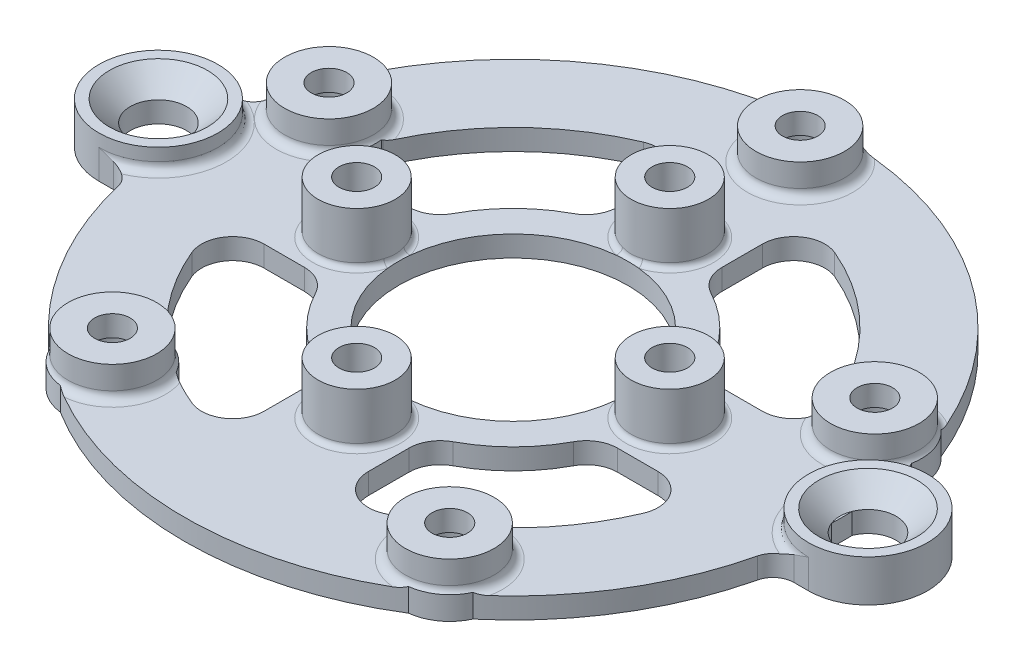
SolidWorks part; units mm, degrees
material "ABS"
ref_plane "Plan de face" through (0, 0, 0) normal (0, 0, 1) x (1, 0, 0)
ref_plane "Plan de dessus" through (0, 0, 0) normal (0, 1, 0) x (1, 0, 0)
ref_plane "Plan de droite" through (0, 0, 0) normal (1, 0, 0) x (0, 0, -1)
sketch "Esquisse1" plane through (0, 0, 0) normal (0, 1, 0) x (1, 0, 0)
  circle A0 centre (0, 0) radius 15 construction
  circle A1 centre (0, 15) radius 1.7
  circle A2 centre (0, 0) radius 31.5
  circle A3 centre (15, 0) radius 1.7
  circle A4 centre (0, -15) radius 1.7
  circle A5 centre (-15, 0) radius 1.7
  circle A6 centre (0, 0) radius 11
  point P15 (0, 0)
  dimension "D1" = 3.4
  dimension "D2" = 30
  dimension "D4" = 22
  dimension "D5" = 63
  dimension "D3" = 4
extrude "Boss.-Extru.1" add sketch "Esquisse1" along normal blind 2
sketch "Esquisse2" plane through (0, 2, 0) normal (0, 1, 0) x (1, 0, 0)
  circle A0 centre (0, -15) radius 1.7 construction
  circle A1 centre (15, 0) radius 1.7 construction
  circle A2 centre (0, 15) radius 1.7 construction
  circle A3 centre (-15, 0) radius 1.7 construction
  circle A4 centre (0, -15) radius 1.7
  circle A5 centre (15, 0) radius 1.7
  circle A6 centre (0, 15) radius 1.7
  circle A7 centre (-15, 0) radius 1.7
  circle A8 centre (0, -15) radius 3.7
  circle A9 centre (15, 0) radius 3.7
  circle A10 centre (0, 15) radius 3.7
  circle A11 centre (-15, 0) radius 3.7
  dimension "D1" = 2
extrude "Boss.-Extru.2" add sketch "Esquisse2" along normal blind 5
sketch "Esquisse3" plane through (0, 0, 0) normal (0, -1, 0) x (1, 0, 0)
  circle A0 centre (15, 0) radius 3
  circle A1 centre (0, -15) radius 3
  circle A2 centre (-15, 0) radius 3
  circle A3 centre (0, 15) radius 3
  point P12 (0, 0)
  dimension "D1" = 6
  dimension "D2" = 4
extrude "Enlèv. mat.-Extru.1" cut sketch "Esquisse3" against normal blind 3
fillet "Congé1" radius 0.5 4 edges at (-15, 2, 3.7) (0, 2, -11.3) (15, 2, 3.7) (0, 2, 18.7)
sketch "Esquisse4" plane through (0, 2, 0) normal (0, 1, 0) x (1, 0, 0)
  line L0 (0, 0) -> (0, -38.4665) construction
  line L1 (34, 0) -> (26, 0) construction
  line L2 (34, -5.7) -> (26, -5.7)
  line L3 (34, 5.7) -> (26, 5.7)
  line L4 (-34, 0) -> (-26, 0) construction
  line L5 (-34, -5.7) -> (-26, -5.7)
  line L6 (-34, 5.7) -> (-26, 5.7)
  circle A0 centre (34, 0) radius 2.7
  arc A2 (34, -5.7) -> (34, 5.7) centre (34, 0) ccw
  arc A3 (26, 5.7) -> (26, -5.7) centre (26, 0) ccw
  arc A4 (-34, -5.7) -> (-34, 5.7) centre (-34, 0) cw
  arc A5 (-26, 5.7) -> (-26, -5.7) centre (-26, 0) cw
  circle A6 centre (-34, 0) radius 2.7
  point P7 (30, 0)
  point P15 (-30, 0)
  dimension "D1" = 5.4
  dimension "D3" = 3
  dimension "D2" = 68
  dimension "D4" = 8
extrude "Boss.-Extru.3" add sketch "Esquisse4" against normal blind 2
sketch "Esquisse5" plane through (0, 2, 0) normal (0, 1, 0) x (1, 0, 0)
  circle A0 centre (-34, 0) radius 2.7 construction
  circle A1 centre (34, 0) radius 2.7 construction
  circle A2 centre (-34, 0) radius 2.7
  circle A3 centre (34, 0) radius 2.7
  circle A4 centre (-34, 0) radius 5.7
  circle A5 centre (34, 0) radius 5.7
  dimension "D1" = 3
extrude "Boss.-Extru.4" add sketch "Esquisse5" along normal blind 2
chamfer "Chanfrein1" distance 2 angle 45 2 edges at (-34, 4, 2.7) (34, 4, 2.7)
sketch "Esquisse6" plane through (0, 2, 0) normal (0, 1, 0) x (1, 0, 0)
  circle A0 centre (0, 0) radius 27.5 construction
  circle A1 centre (0, 27.5) radius 1.7
  circle A2 centre (0, 27.5) radius 2.5 construction
  circle A3 centre (0, 0) radius 25 construction
  circle A4 centre (26.1541, 8.498) radius 1.7
  circle A5 centre (26.1541, 8.498) radius 2.5 construction
  circle A6 centre (16.1641, -22.248) radius 1.7
  circle A7 centre (16.1641, -22.248) radius 2.5 construction
  circle A8 centre (-16.1641, -22.248) radius 1.7
  circle A9 centre (-16.1641, -22.248) radius 2.5 construction
  circle A10 centre (-26.1541, 8.498) radius 1.7
  circle A11 centre (-26.1541, 8.498) radius 2.5 construction
  point P21 (0, 0)
  dimension "D1" = 3.4
  dimension "D2" = 5
  dimension "D3" = 50
  dimension "D5" = 55
  dimension "D4" = 5
extrude "Enlèv. mat.-Extru.2" cut sketch "Esquisse6" against normal blind 2
fillet "Congé4" radius 2 4 edges at (30.98, 1, 5.7) (30.98, 1, -5.7) (-30.98, 1, 5.7) (-30.98, 1, -5.7)
sketch "Esquisse7" plane through (0, 2, 0) normal (0, 1, 0) x (1, 0, 0)
  line L0 (0, 27.5) -> (0, 0) construction
  line L1 (5, 22.9619) -> (5, 13.0767)
  line L2 (-5, 22.9619) -> (-5, 13.0767)
  line L3 (22.9619, 5) -> (13.0767, 5)
  line L4 (22.9619, -5) -> (13.0767, -5)
  line L5 (5, -22.9619) -> (5, -13.0767)
  line L6 (-5, -22.9619) -> (-5, -13.0767)
  line L7 (-22.9619, -5) -> (-13.0767, -5)
  line L8 (-22.9619, 5) -> (-13.0767, 5)
  arc A0 (-13.0767, -5) -> (-5, -13.0767) centre (0, 0) ccw
  arc A1 (5, -22.9619) -> (22.9619, -5) centre (0, 0) ccw
  arc A2 (30.6566, 7.2403) -> (-30.6566, 7.2403) centre (0, 0) ccw construction
  arc A3 (-5, 13.0767) -> (-13.0767, 5) centre (0, 0) ccw
  arc A4 (13.0767, 5) -> (5, 13.0767) centre (0, 0) ccw
  arc A5 (5, -13.0767) -> (13.0767, -5) centre (0, 0) ccw
  arc A6 (-22.9619, -5) -> (-5, -22.9619) centre (0, 0) ccw
  arc A7 (-5, 22.9619) -> (-22.9619, 5) centre (0, 0) ccw
  arc A8 (22.9619, 5) -> (5, 22.9619) centre (0, 0) ccw
  point P28 (0, 0)
  dimension "D1" = 8
  dimension "D2" = 28
  dimension "D3" = 10
  dimension "D4" = 4
extrude "Enlèv. mat.-Extru.3" cut sketch "Esquisse7" against normal blind 2
fillet "Congé5" radius 3 16 edges at (5, 1, -13.0767) (13.0767, 1, -5) (13.0767, 1, 5) (5, 1, 13.0767) (-13.0767, 1, -5) (-22.9619, 1, 5) (-13.0767, 1, 5) (-5, 1, 13.0767) (-5, 1, 22.9619) (5, 1, 22.9619) (22.9619, 1, 5) (22.9619, 1, -5) (5, 1, -22.9619) (-22.9619, 1, -5) (-5, 1, -13.0767) (-5, 1, -22.9619)
sketch "Esquisse8" plane through (0, 2, 0) normal (0, 1, 0) x (1, 0, 0)
  circle A0 centre (0, 27.5) radius 4.25
  circle A1 centre (26.1541, 8.498) radius 4.25
  circle A2 centre (16.1641, -22.248) radius 4.25
  circle A3 centre (-16.1641, -22.248) radius 4.25
  circle A4 centre (-26.1541, 8.498) radius 4.25
  circle A5 centre (-16.1641, -22.248) radius 1.7 construction
  circle A6 centre (16.1641, -22.248) radius 1.7 construction
  circle A7 centre (26.1541, 8.498) radius 1.7 construction
  circle A8 centre (0, 27.5) radius 1.7 construction
  circle A9 centre (-26.1541, 8.498) radius 1.7 construction
  circle A10 centre (-16.1641, -22.248) radius 1.7
  circle A11 centre (16.1641, -22.248) radius 1.7
  circle A12 centre (26.1541, 8.498) radius 1.7
  circle A13 centre (0, 27.5) radius 1.7
  circle A14 centre (-26.1541, 8.498) radius 1.7
  point P13 (0, 0)
  dimension "D2" = 8.5
  dimension "D1" = 5
extrude "Boss.-Extru.5" add sketch "Esquisse8" along normal blind 3
sketch "Esquisse9" plane through (0, 0, 0) normal (0, -1, 0) x (1, 0, 0)
  circle A0 centre (26.1541, -8.498) radius 4.5
  circle A1 centre (0, -27.5) radius 4.5
  circle A2 centre (-26.1541, -8.498) radius 4.5
  circle A3 centre (-16.1641, 22.248) radius 4.5
  circle A4 centre (16.1641, 22.248) radius 4.5
  circle A5 centre (0, -27.5) radius 1.7 construction
  circle A6 centre (-26.1541, -8.498) radius 1.7 construction
  circle A7 centre (-16.1641, 22.248) radius 1.7 construction
  circle A8 centre (16.1641, 22.248) radius 1.7 construction
  circle A9 centre (26.1541, -8.498) radius 1.7 construction
  circle A10 centre (0, -27.5) radius 1.7
  circle A11 centre (-26.1541, -8.498) radius 1.7
  circle A12 centre (-16.1641, 22.248) radius 1.7
  circle A13 centre (16.1641, 22.248) radius 1.7
  circle A14 centre (26.1541, -8.498) radius 1.7
  point P13 (0, 0)
  dimension "D1" = 9
  dimension "D2" = 5
extrude "Boss.-Extru.6" add sketch "Esquisse9" against normal blind 2
fillet "Congé6" radius 0.8 20 edges at (33.3015, 2, -5.7) (-33.3015, 2, 5.7) (-28.3, 2, 0) (28.3, 2, 0) (33.3015, 2, 5.7) (-33.3015, 2, -5.7) (0, 2, -23.25) (26.1541, 2, -4.248) (16.1641, 2, 26.498) (-16.1641, 2, 26.498) (-26.1541, 2, -4.248) (30.4338, 2, -9.8885) (21.6645, 2, -8.1909) (0, 2, -32) (-30.4338, 2, -9.8885) (-21.6645, 2, -8.1909) (-18.8091, 2, 25.8885) (-13.5191, 2, 18.6074) (18.8091, 2, 25.8885) (13.5191, 2, 18.6074)
sketch "Esquisse10" plane through (0, 0, 0) normal (0, -1, 0) x (1, 0, 0)
  circle A1 centre (0, -27.5) radius 2.9
  circle A2 centre (-26.1541, -8.498) radius 2.9
  circle A3 centre (-16.1641, 22.248) radius 2.9
  circle A4 centre (16.1641, 22.248) radius 2.9
  circle A5 centre (26.1541, -8.498) radius 2.9
  point P13 (0, 0)
  dimension "D1" = 5.8
  dimension "D2" = 5
extrude "Enlèv. mat.-Extru.4" cut sketch "Esquisse10" against normal blind 3
